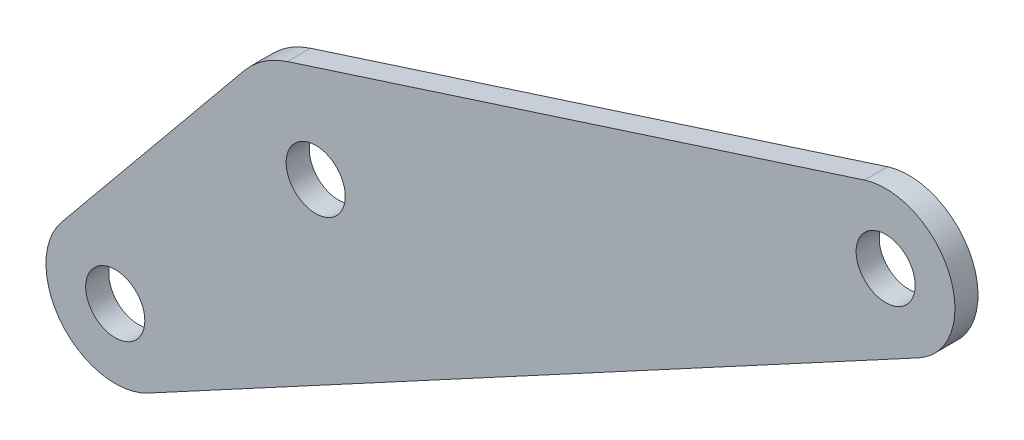
SolidWorks part; units mm, degrees
ref_plane "Front Plane" through (0, 0, 0) normal (0, 0, 1) x (1, 0, 0)
ref_plane "Top Plane" through (0, 0, 0) normal (0, 1, 0) x (1, 0, 0)
ref_plane "Right Plane" through (0, 0, 0) normal (1, 0, 0) x (0, 0, -1)
sketch "Sketch1" plane through (0, 0, 0) normal (0, 0, 1) x (1, 0, 0)
  line L0 (-17.4609, -11.2661) -> (-4.9086, 4.0285)
  line L1 (37.7194, 18.8206) -> (-1.9468, 6.0442)
  line L2 (41.441, 10.0962) -> (-11.518, -18.4788)
  circle A0 centre (0, 0) radius 2.032
  circle A1 centre (-13.7795, -14.2875) radius 2.032
  circle A3 centre (39.1795, 14.2875) radius 2.032
  arc A4 (-1.9468, 6.0442) -> (-4.9086, 4.0285) centre (0, 0) ccw
  arc A5 (-17.4609, -11.2661) -> (-11.518, -18.4788) centre (-13.7795, -14.2875) ccw
  arc A6 (37.7194, 18.8206) -> (41.441, 10.0962) centre (39.1795, 14.2875) cw
  circle A7 centre (39.1795, 14.2875) radius 2.032 construction
  circle A8 centre (-13.7795, -14.2875) radius 2.032 construction
  point P13 (35.9855, 14.0389)
  point P14 (-14.5222, -18.2006)
  dimension "D1" = 4.064
  dimension "D2" = 4.064
  dimension "D3" = 6.35
  dimension "D4" = 4.7625
extrude "Boss-Extrude1" add sketch "Sketch1" along normal blind 1.5875
